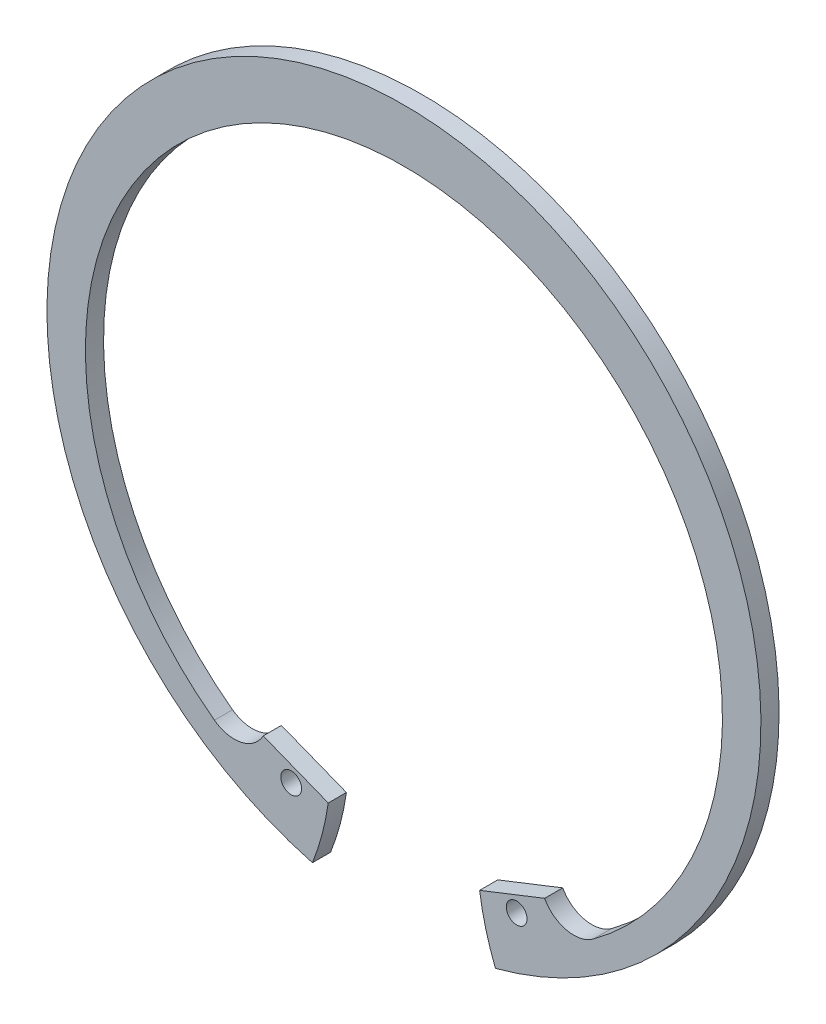
SolidWorks part; units mm, degrees
material "Plain Carbon Steel"
ref_plane "Front Plane" through (0, 0, 0) normal (0, 0, 1) x (1, 0, 0)
ref_plane "Top Plane" through (0, 0, 0) normal (0, 1, 0) x (1, 0, 0)
ref_plane "Right Plane" through (0, 0, 0) normal (1, 0, 0) x (0, 0, -1)
sketch "Sketch1" plane through (0, 0, 0) normal (0, 0, 1) x (1, 0, 0)
  line L0 (0, 54.4957) -> (0, 46.3931) construction
  line L1 (-31.2574, -44.6403) -> (-28.9264, -41.3112) construction
  line L2 (0, 0) -> (0, -54.4957) construction
  line L3 (-11.3157, -43.655) -> (-13.6738, -52.7523) construction
  line L4 (-11.3157, -43.655) -> (-14.4907, -43.655) construction
  circle A0 centre (0, 0) radius 52.1589 construction
  circle A1 centre (0, 0) radius 54.4957 construction
  circle A2 centre (0, 0) radius 49.2125 construction
  dimension "Ring OD" = 108.9914
  dimension "For ID" = 98.425
  dimension "Maximum Section" = 8.1026
  dimension "D1" = 145
  dimension "Minimum Section" = 4.064
  dimension "Gap Width" = 22.6314
  dimension "Lug Height" = 9.398
  dimension "Hole Diameter" = 3.175
sketch "Sketch2" plane through (0, 0, 0) normal (1, 0, 0) x (0, 0, -1)
  line L0 (-1.524, 54.4957) -> (1.524, 54.4957) construction
  line L1 (-1.3843, -54.4957) -> (1.3843, -54.4957) construction
  point P3 (0, 54.4957)
  point P7 (0, -54.4957)
  point P8 (-1.3843, -54.4957)
  point P10 (1.3843, -54.4957)
  point P11 (-1.524, 54.4957)
  point P12 (1.524, 54.4957)
  dimension "For Groove Width" = 3.048
  dimension "Ring Thickness" = 2.7686
sketch "Sketch3" plane through (0, 0, 0) normal (0, 0, 1) x (1, 0, 0)
  line L0 (-13.6738, -52.7523) -> (-11.3157, -43.655)
  line L1 (-11.3157, -43.655) -> (-21.4761, -39.6558)
  line L2 (0, 0) -> (-16.3959, -41.6554) construction
  line L3 (-28.9264, -41.3112) -> (28.9264, -41.3112) construction
  line L4 (0, 0) -> (0, -54.4957) construction
  line L5 (-21.4761, -39.6558) -> (0, 0) construction
  line L6 (-16.3959, -41.6554) -> (-17.2102, -43.7241) construction
  line L7 (-17.2102, -43.7241) -> (-18.0244, -45.7929) construction
  line L8 (0, 54.4957) -> (0, 46.3931) construction
  line L9 (11.3157, -43.655) -> (21.4761, -39.6558)
  line L10 (13.6738, -52.7523) -> (11.3157, -43.655)
  arc A0 (-13.6738, -52.7523) -> (13.6738, -52.7523) centre (0, 0) cw
  circle A1 centre (0, 0) radius 54.4957 construction
  arc A2 (-28.9264, -41.3112) -> (28.9264, -41.3112) centre (0, -2.2293) cw
  arc A3 (-28.9264, -41.3112) -> (-21.4761, -39.6558) centre (-25.9199, -37.2492) ccw
  circle A4 centre (-17.2102, -43.7241) radius 1.5875
  circle A5 centre (0, 0) radius 50.4317 construction
  arc A6 (28.9264, -41.3112) -> (21.4761, -39.6558) centre (25.9199, -37.2492) cw
  circle A7 centre (17.2102, -43.7241) radius 1.5875
  circle A8 centre (0, 0) radius 49.2125 construction
  point P3 (0, -41.3112)
  dimension "D1" = 3.175
extrude "Boss-Extrude1" add sketch "Sketch3" against normal up to vertex (1.3843 mm away) and the other way up to vertex (1.3843 mm away) up to point (0, -54.4957, -1.3843) other way up to point (0, -54.4957, 1.3843)
sketch "Sketch4" plane through (0, 0, 0) normal (0, 0, 1) x (1, 0, 0)
  line L0 (-11.3157, -43.655) -> (-21.4761, -39.6558) construction
  line L1 (-11.3157, -43.655) -> (-13.6738, -52.7523) construction
  line L2 (-13.9687, -52.675) -> (-11.5521, -43.562) construction
  line L3 (-11.5521, -43.562) -> (0, 0) construction
  line L4 (-13.9687, -52.675) -> (-13.9687, -66.6437)
  line L5 (-13.9687, -66.6437) -> (0, -66.6437)
  line L6 (0, -66.6437) -> (0, -54.4957)
  line L7 (0, -54.4957) -> (0, -43.562)
  line L8 (0, 0) -> (0, -54.4957) construction
  line L9 (0, -43.562) -> (-11.5521, -43.562)
  arc A0 (-11.5521, -43.562) -> (-13.9687, -52.675) centre (-51.2749, -37.9049) cw
  circle A1 centre (0, 0) radius 54.4957 construction
  dimension "D1" = 0.254
extrude "Cut-Extrude1" cut sketch "Sketch4" against normal through all both and the other way through all
mirror "Mirror1" about plane through (0, 0, 0) normal (1, 0, 0) of "Cut-Extrude1"
equation "\"D1@Sketch3\"=\"Hole Diameter@Sketch1\""
